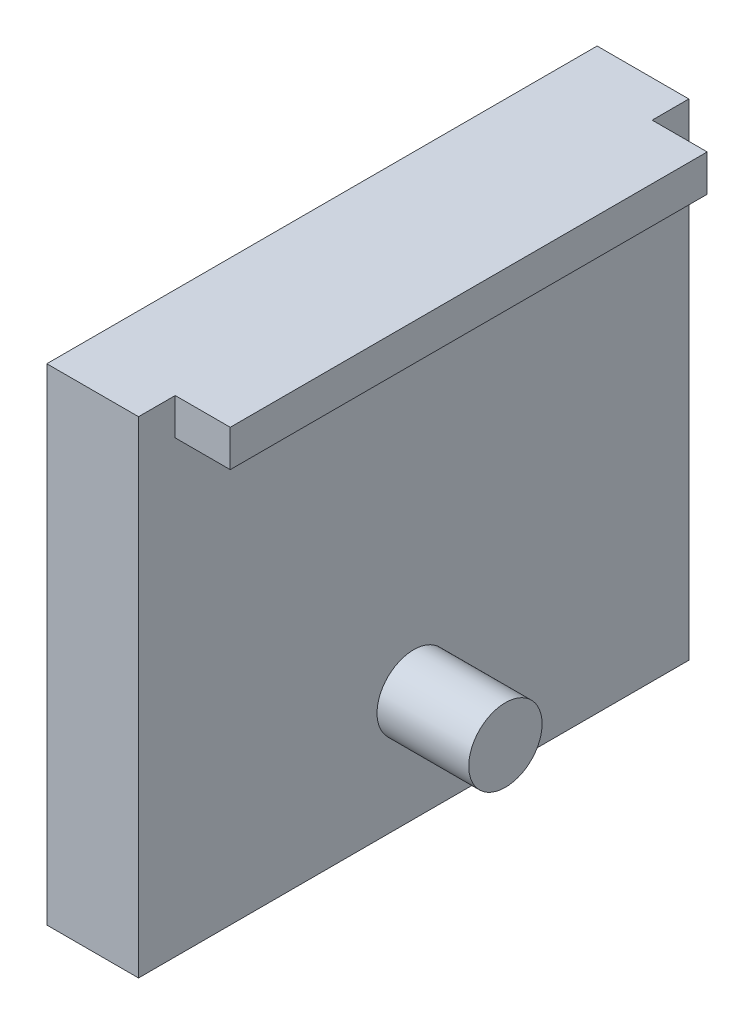
SolidWorks part; units mm, degrees
ref_plane "Front Plane" through (0, 0, 0) normal (0, 0, 1) x (1, 0, 0)
ref_plane "Top Plane" through (0, 0, 0) normal (0, 1, 0) x (1, 0, 0)
ref_plane "Right Plane" through (0, 0, 0) normal (1, 0, 0) x (0, 0, -1)
ref_plane "Plane1" through (-181, 0, 0) normal (1, 0, 0) x (0, 0, -1)
sketch "Sketch1" plane through (-181, 0, 0) normal (1, 0, 0) x (0, 0, -1)
  line L0 (-134, 37) -> (-134, 63.5)
  line L1 (-134, 63.5) -> (-164, 63.5)
  line L2 (-164, 63.5) -> (-164, 37)
  line L3 (-164, 37) -> (-134, 37)
extrude "Boss-Extrude1" add sketch "Sketch1" along normal mid plane 5
ref_plane "Plane2" through (-183.5, 0, 0) normal (1, 0, 0) x (0, 0, -1)
sketch "Sketch2" plane through (-183.5, 0, 0) normal (1, 0, 0) x (0, 0, -1)
  line L0 (-138, 40) -> (-138, 42)
  line L1 (-138, 42) -> (-160, 42)
  line L2 (-160, 42) -> (-160, 40)
  line L3 (-160, 40) -> (-138, 40)
  line L4 (-138, 44) -> (-138, 46)
  line L5 (-138, 46) -> (-160, 46)
  line L6 (-160, 46) -> (-160, 44)
  line L7 (-160, 44) -> (-138, 44)
extrude "Boss-Extrude2" add sketch "Sketch2" along normal mid plane 1
ref_plane "Plane3" through (-177, 0, 0) normal (1, 0, 0) x (0, 0, -1)
sketch "Sketch3" plane through (-177, 0, 0) normal (1, 0, 0) x (0, 0, -1)
  line L0 (-136, 61.5) -> (-136, 63.5)
  line L1 (-136, 63.5) -> (-162, 63.5)
  line L2 (-162, 63.5) -> (-162, 61.5)
  line L3 (-162, 61.5) -> (-136, 61.5)
extrude "Boss-Extrude3" add sketch "Sketch3" along normal mid plane 3
ref_plane "Plane4" through (-176, 0, 0) normal (1, 0, 0) x (0, 0, -1)
sketch "Sketch4" plane through (-176, 0, 0) normal (1, 0, 0) x (0, 0, -1)
  circle A0 centre (-149, 43) radius 2
extrude "Boss-Extrude4" add sketch "Sketch4" along normal mid plane 5
